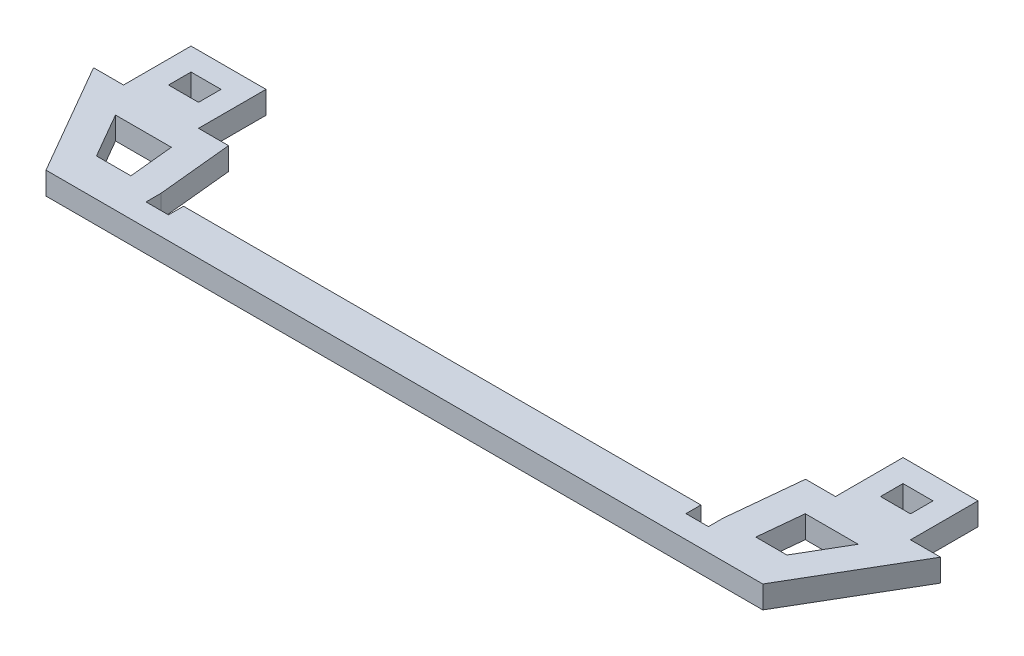
SolidWorks part; units mm, degrees
ref_plane "Front Plane" through (0, 0, 0) normal (0, 0, 1) x (1, 0, 0)
ref_plane "Top Plane" through (0, 0, 0) normal (0, 1, 0) x (1, 0, 0)
ref_plane "Right Plane" through (0, 0, 0) normal (1, 0, 0) x (0, 0, -1)
sketch "Sketch1" plane through (0, 0, 0) normal (0, 1, 0) x (1, 0, 0)
  line L0 (-62.4186, -47.1587) -> (-58.4186, -47.1587)
  line L1 (-58.4186, -47.1587) -> (-58.4186, -38.1587)
  line L2 (-58.4186, -38.1587) -> (-48.4186, -38.1587)
  line L3 (-48.4186, -38.1587) -> (-48.4186, -47.1587)
  line L4 (-48.4186, -47.1587) -> (-44.4186, -47.1587)
  line L5 (-44.4186, -47.1587) -> (-43.4188, -57.1562)
  line L7 (31.5814, -57.2088) -> (32.5814, -47.2113)
  line L8 (32.5814, -47.2113) -> (36.5814, -47.2113)
  line L9 (36.5814, -47.2113) -> (36.5814, -38.2113)
  line L10 (36.5814, -38.2113) -> (46.5814, -38.2113)
  line L11 (46.5814, -38.2113) -> (46.5814, -47.2113)
  line L12 (46.5814, -47.2113) -> (50.5814, -47.2113)
  line L13 (50.5814, -47.2113) -> (41.8306, -62.1587)
  line L14 (41.8306, -62.1587) -> (-53.7583, -62.1587)
  line L15 (-53.7583, -62.1587) -> (-62.4186, -47.1587)
  line L16 (36.5478, -51.2113) -> (43.6046, -51.2113)
  line L17 (-55.4186, -41.1587) -> (-51.4186, -41.1587)
  line L18 (-55.4186, -41.1587) -> (-55.4186, -44.1587)
  line L19 (-55.4186, -44.1587) -> (-51.4186, -44.1587)
  line L20 (-51.4186, -41.1587) -> (-51.4186, -44.1587)
  line L21 (39.5814, -41.2113) -> (43.5814, -41.2113)
  line L22 (39.5814, -41.2113) -> (39.5814, -44.2113)
  line L23 (39.5814, -44.2113) -> (43.5814, -44.2113)
  line L24 (43.5814, -41.2113) -> (43.5814, -44.2113)
  line L25 (43.6046, -51.2113) -> (40.0934, -57.2088)
  line L26 (40.0934, -57.2088) -> (35.9479, -57.2088)
  line L27 (35.9479, -57.2088) -> (36.5478, -51.2113)
  line L28 (-55.4904, -51.1587) -> (-48.0385, -51.1587)
  line L29 (-48.0385, -51.1587) -> (-47.4385, -57.1587)
  line L30 (-47.4385, -57.1587) -> (-52.0263, -57.1587)
  line L31 (-52.0263, -57.1587) -> (-55.4904, -51.1587)
  line L32 (28.5814, -57.1587) -> (28.5814, -59.1587)
  line L33 (28.5814, -47.1587) -> (28.5814, -62.1587) construction
  line L34 (28.5814, -59.1587) -> (31.5814, -59.1587)
  line L35 (31.5814, -59.1587) -> (31.5814, -57.2088)
  line L36 (31.5814, -62.1587) -> (31.5814, -47.1587) construction
  line L38 (-43.4188, -57.1562) -> (-43.4188, -59.1587)
  line L39 (-43.4188, -59.1587) -> (-40.4188, -59.1587)
  line L40 (-40.4188, -59.1587) -> (-40.4188, -57.1587)
  line L41 (-40.4188, -57.1587) -> (28.5814, -57.1587)
  point P7 (-43.5277, -57.1587)
  point P42 (0, 0)
  point P47 (32.5901, -57.1275)
  point P48 (31.6958, -57.1218)
  dimension "D1" = 15
  dimension "D2" = 4
  dimension "D3" = 9
  dimension "D4" = 3
  dimension "D5" = 3
  dimension "D7" = 120
  dimension "D8" = 10
  dimension "D9" = 85
  dimension "D10" = 3
  dimension "D11" = 3
  dimension "D12" = 3
  dimension "D13" = 3
  dimension "D14" = 3
  dimension "D15" = 3
  dimension "D17" = 4
  dimension "D18" = 4
  dimension "D19" = 4
  dimension "D20" = 4
  dimension "D21" = 4
  dimension "D23" = 2
  dimension "D24" = 3
extrude "Boss-Extrude1" add sketch "Sketch1" along normal blind 3
